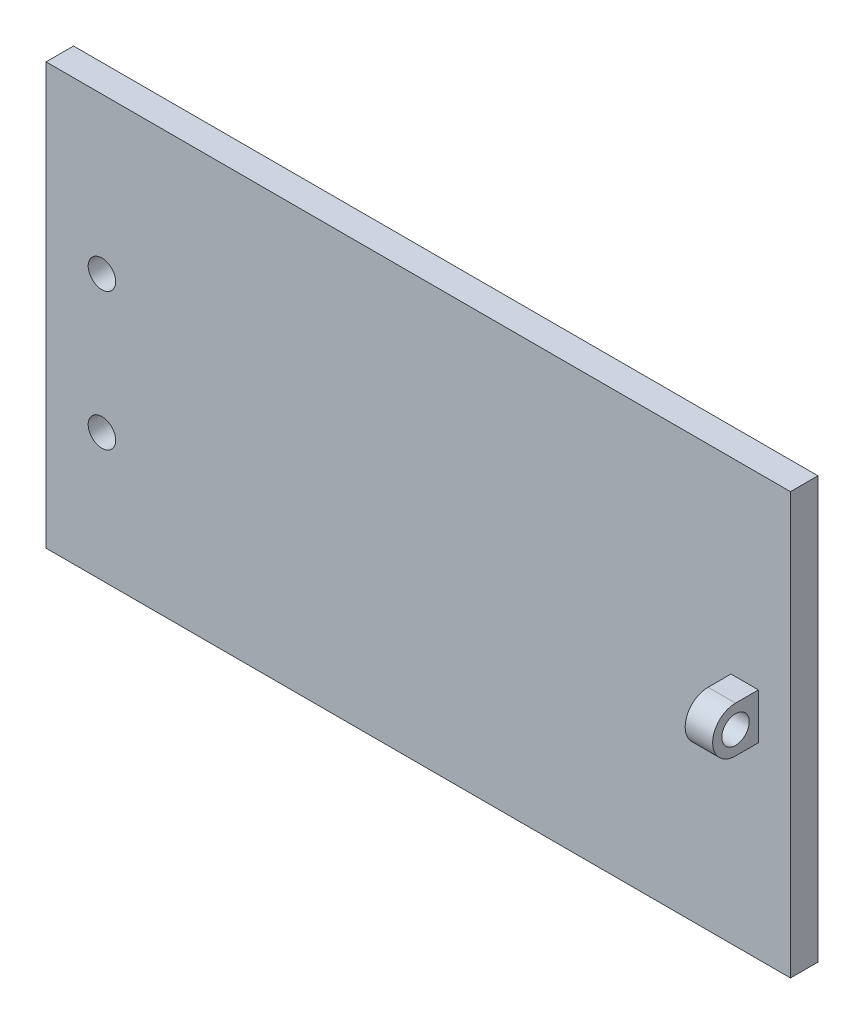
SolidWorks part; units mm, degrees
ref_plane "Front Plane" through (0, 0, 0) normal (0, 0, 1) x (1, 0, 0)
ref_plane "Top Plane" through (0, 0, 0) normal (0, 1, 0) x (1, 0, 0)
ref_plane "Right Plane" through (0, 0, 0) normal (1, 0, 0) x (0, 0, -1)
sketch "Sketch1" plane through (0, 0, 0) normal (0, 0, 1) x (1, 0, 0)
  line L1 (-40.65, 23) -> (40.65, 23)
  line L2 (-40.65, 23) -> (-40.65, -23)
  line L3 (-40.65, -23) -> (40.65, -23)
  line L4 (40.65, 23) -> (40.65, -23)
  line L5 (-40.65, 23) -> (40.65, -23) construction
  line L6 (-40.65, -23) -> (40.65, 23) construction
  point P0 (0, 0)
  dimension "D1" = 46
  dimension "D2" = 81.3
extrude "Boss-Extrude1" add sketch "Sketch1" against normal blind 3
sketch "Sketch5" plane through (0, 0, 0) normal (0, 0, 1) x (1, 0, 0)
  line L0 (40.65, 0) -> (35.65, 0) construction
  line L1 (40.65, -23) -> (40.65, 23) construction
  line L3 (34.15, 2.5) -> (37.15, 2.5)
  line L4 (34.15, 2.5) -> (34.15, -2.5)
  line L5 (34.15, -2.5) -> (37.15, -2.5)
  line L6 (37.15, 2.5) -> (37.15, -2.5)
  line L7 (34.15, 2.5) -> (37.15, -2.5) construction
  line L8 (34.15, -2.5) -> (37.15, 2.5) construction
  dimension "D1" = 5
  dimension "D2" = 3
  dimension "D3" = 5
extrude "Boss-Extrude3" add sketch "Sketch5" along normal blind 5
sketch "Sketch6" plane through (0, 0, 0) normal (1, 0, 0) x (0, 0, -1)
  line L0 (-2.5, 2.5) -> (-2.5, -2.5) construction
  line L1 (-5, 2.5) -> (0, 2.5) construction
  line L2 (-5, -2.5) -> (0, -2.5) construction
  circle A0 centre (-2.5, 0) radius 1.5
  dimension "D1" = 3
extrude "Cut-Extrude2" cut sketch "Sketch6" along normal through all
fillet "Fillet5" 2 edges at (35.65, 2.5, 5) (35.65, -2.5, 5) type full round first side face at (35.65, 2.5, 2.5) second side face at (35.65, -2.5, 2.5) middle face at (35.65, 0, 5)
sketch "Sketch7" plane through (0, 0, 0) normal (0, 0, 1) x (1, 0, 0)
  line L0 (-40.65, 0) -> (-34.55, 0)
  line L1 (-40.65, 23) -> (-40.65, -23) construction
  line L2 (-34.55, 0) -> (-34.55, -9)
  circle A0 centre (-34.55, -9) radius 1.5
  circle A3 centre (-34.55, 6) radius 1.5
  dimension "D3" = 3
  dimension "D4" = 3
  dimension "D1" = 6.1
  dimension "D2" = 9
  dimension "D5" = 15
  dimension "D6" = 6.1
extrude "Cut-Extrude3" cut sketch "Sketch7" against normal blind 10 contours A3 | A0
